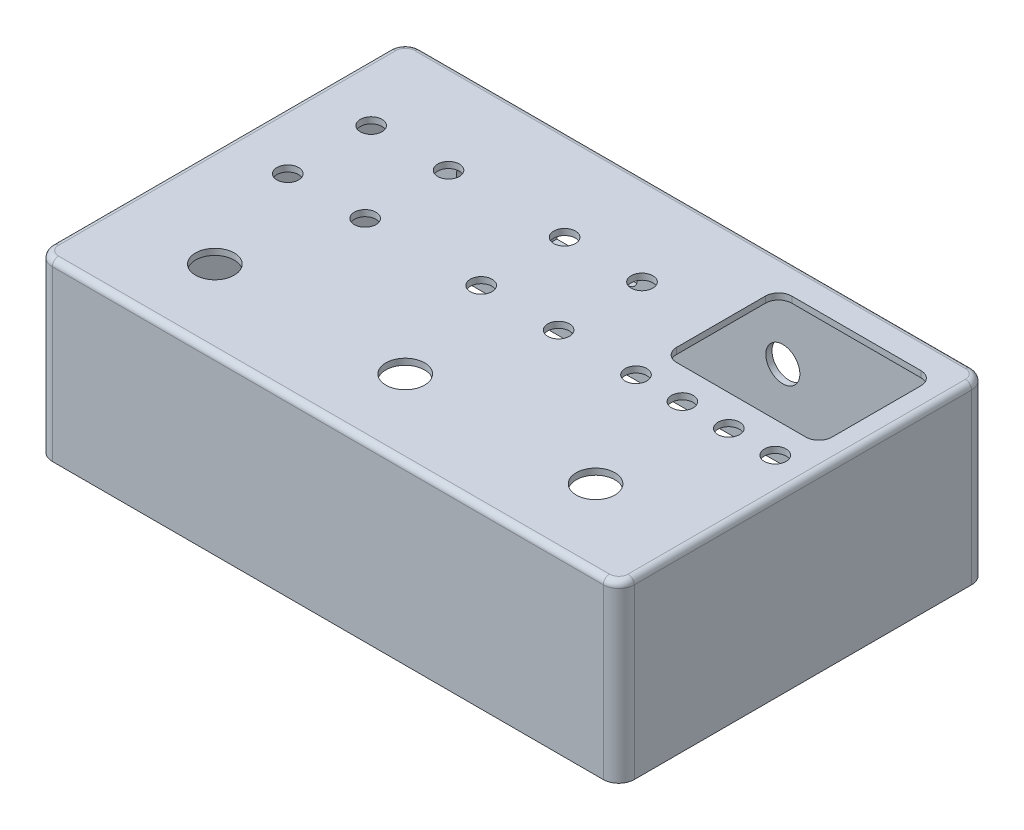
SolidWorks part; units mm, degrees
ref_plane "前视基准面" through (0, 0, 0) normal (0, 0, 1) x (1, 0, 0)
ref_plane "上视基准面" through (0, 0, 0) normal (0, 1, 0) x (1, 0, 0)
ref_plane "右视基准面" through (0, 0, 0) normal (1, 0, 0) x (0, 0, -1)
sketch "草图1" plane through (0, 0, 0) normal (0, 1, 0) x (1, 0, 0)
  line L0 (-67.19, 26.9473) -> (101.81, 26.9473) construction
  line L1 (-86.19, 56.9473) -> (101.81, 56.9473)
  line L2 (-86.19, 56.9473) -> (-86.19, -62.0527)
  line L3 (-86.19, -62.0527) -> (101.81, -62.0527)
  line L4 (101.81, 56.9473) -> (101.81, -62.0527)
  line L5 (-86.19, 26.9473) -> (-67.19, 26.9473) construction
  line L6 (-86.19, 0) -> (101.81, 0) construction
  line L7 (-86.19, -37.0527) -> (101.81, -37.0527) construction
  line L9 (48.445, 46.9473) -> (90.175, 46.9473)
  line L10 (44.445, 42.9473) -> (44.445, 14.2473)
  line L11 (48.445, 10.2473) -> (90.175, 10.2473)
  line L12 (94.175, 42.9473) -> (94.175, 14.2473)
  circle A0 centre (-67.19, 26.9473) radius 3.5
  circle A1 centre (-42.19, 26.9473) radius 3.5
  circle A2 centre (-67.19, 0) radius 3.5
  circle A3 centre (-42.19, 0) radius 3.5
  circle A4 centre (-4.69, 26.9473) radius 3.5
  circle A5 centre (20.31, 26.9473) radius 3.5
  circle A6 centre (-4.69, 0) radius 3.5
  circle A7 centre (20.31, 0) radius 3.5
  circle A8 centre (45.31, 0) radius 3.5
  circle A9 centre (60.31, 0) radius 3.5
  circle A10 centre (75.31, 0) radius 3.5
  circle A11 centre (90.31, 0) radius 3.5
  circle A12 centre (-53.69, -37.0527) radius 6.25
  circle A13 centre (7.81, -37.0527) radius 6.25
  circle A14 centre (69.31, -37.0527) radius 6.25
  arc A15 (90.175, 46.9473) -> (94.175, 42.9473) centre (90.175, 42.9473) cw
  arc A16 (48.445, 46.9473) -> (44.445, 42.9473) centre (48.445, 42.9473) ccw
  arc A17 (90.175, 10.2473) -> (94.175, 14.2473) centre (90.175, 14.2473) ccw
  arc A18 (44.445, 14.2473) -> (48.445, 10.2473) centre (48.445, 14.2473) ccw
  point P43 (69.31, 46.9473)
  point P44 (43.191, 0)
  point P49 (94.175, 46.9473)
  point P52 (44.445, 46.9473)
  point P55 (94.175, 10.2473)
  dimension "D3" = 30
  dimension "D12" = 7
  dimension "D16" = 12.5
  dimension "D19" = 49.73
  dimension "D23" = 4
  dimension "D1" = 188
  dimension "D2" = 119
  dimension "D4" = 19
  dimension "D5" = 25
  dimension "D6" = 25
  dimension "D7" = 37.5
  dimension "D8" = 25
  dimension "D9" = 15
  dimension "D10" = 15
  dimension "D11" = 15
  dimension "D13" = 32.5
  dimension "D14" = 61.5
  dimension "D15" = 61.5
  dimension "D18" = 19
  dimension "D20" = 36.7
  dimension "D21" = 10
  dimension "D22" = 25
extrude "凸台-拉伸1" add sketch "草图1" along normal blind 56.5
sketch "草图3" plane through (0, 0, 0) normal (0, -1, 0) x (1, 0, 0)
  line L1 (98.81, -53.9473) -> (-83.19, -53.9473)
  line L2 (98.81, -53.9473) -> (98.81, 59.0527)
  line L3 (98.81, 59.0527) -> (-83.19, 59.0527)
  line L4 (-86.19, 62.0527) -> (-86.19, -56.9473)
  line L5 (-86.19, -56.9473) -> (101.81, -56.9473)
  line L6 (101.81, -56.9473) -> (101.81, 62.0527)
  line L7 (101.81, 62.0527) -> (-86.19, 62.0527)
  line L8 (-86.19, 62.0527) -> (-86.19, -56.9473)
  line L9 (-86.19, -56.9473) -> (101.81, -56.9473)
  line L10 (101.81, -56.9473) -> (101.81, 62.0527)
  line L11 (101.81, 62.0527) -> (-86.19, 62.0527)
  line L12 (-83.19, -53.9473) -> (-83.19, 59.0527)
  circle M9 centre (69.31, 37.0527) radius 6.25
  circle M10 centre (7.81, 37.0527) radius 6.25
  circle M11 centre (-53.69, 37.0527) radius 6.25
  circle M12 centre (90.31, 0) radius 3.5
  circle M13 centre (75.31, 0) radius 3.5
  circle M14 centre (60.31, 0) radius 3.5
  circle M15 centre (45.31, 0) radius 3.5
  circle M16 centre (20.31, 0) radius 3.5
  circle M17 centre (-4.69, 0) radius 3.5
  circle M18 centre (20.31, -26.9473) radius 3.5
  circle M19 centre (-4.69, -26.9473) radius 3.5
  circle M20 centre (-42.19, 0) radius 3.5
  circle M21 centre (-67.19, 0) radius 3.5
  circle M22 centre (-42.19, -26.9473) radius 3.5
  circle M23 centre (-67.19, -26.9473) radius 3.5
  arc M28 (94.175, -42.9473) -> (90.175, -46.9473) centre (90.175, -42.9473) cw
  line M29 (90.175, -46.9473) -> (48.445, -46.9473)
  arc M30 (48.445, -46.9473) -> (44.445, -42.9473) centre (48.445, -42.9473) cw
  line M31 (44.445, -42.9473) -> (44.445, -14.2473)
  arc M32 (44.445, -14.2473) -> (48.445, -10.2473) centre (48.445, -14.2473) cw
  line M33 (48.445, -10.2473) -> (90.175, -10.2473)
  arc M34 (90.175, -10.2473) -> (94.175, -14.2473) centre (90.175, -14.2473) cw
  line M35 (94.175, -14.2473) -> (94.175, -42.9473)
  dimension "D2" = 3
  dimension "D3" = 3
  dimension "D4" = 3
  dimension "D5" = 3
  dimension "D1" = 0
extrude "切除-拉伸2" cut sketch "草图3" against normal offset from surface (53.5 mm away) 3 contours L12 L1 L2 L3 M10 M12 M14 M16 M18 M20 M22 M35 M28 M29 M30 M31 M32 M33 M34 M23 M21 M19 M17 M15 M13 M11 M9 region at (1.6167, 0, 5.2891) up to face at (7.81, 56.5, 43.3027)
sketch "草图4" plane through (0, 56.5, 0) normal (0, 1, 0) x (1, 0, 0)
  line L0 (90.175, 46.9473) -> (48.445, 46.9473)
  line L1 (90.175, 46.9473) -> (48.445, 46.9473)
  line L2 (44.445, 42.9473) -> (44.445, 14.2473)
  line L3 (44.445, 42.9473) -> (44.445, 14.2473)
  line L4 (94.175, 14.2473) -> (94.175, 42.9473)
  line L5 (94.175, 14.2473) -> (94.175, 42.9473)
  line L6 (48.445, 10.2473) -> (90.175, 10.2473)
  line L7 (48.445, 10.2473) -> (90.175, 10.2473)
  arc A0 (48.445, 46.9473) -> (44.445, 42.9473) centre (48.445, 42.9473) ccw
  arc A1 (48.445, 46.9473) -> (44.445, 42.9473) centre (48.445, 42.9473) ccw
  arc A2 (44.445, 14.2473) -> (48.445, 10.2473) centre (48.445, 14.2473) ccw
  arc A3 (44.445, 14.2473) -> (48.445, 10.2473) centre (48.445, 14.2473) ccw
  arc A4 (94.175, 42.9473) -> (90.175, 46.9473) centre (90.175, 42.9473) ccw
  arc A5 (94.175, 42.9473) -> (90.175, 46.9473) centre (90.175, 42.9473) ccw
  arc A6 (90.175, 10.2473) -> (94.175, 14.2473) centre (90.175, 14.2473) ccw
  arc A7 (90.175, 10.2473) -> (94.175, 14.2473) centre (90.175, 14.2473) ccw
extrude "切除-拉伸-薄壁1" cut sketch "草图4" against normal blind 3 thin thin type one direction wall 0.25
fillet "圆角1" radius 5 8 edges at (-86.19, 28.25, -56.9473) (-86.19, 28.25, 62.0527) (-83.19, 26.75, 59.0527) (98.81, 26.75, -53.9473) (101.81, 28.25, -56.9473) (101.81, 28.25, 62.0527) (98.81, 26.75, 59.0527) (-83.19, 26.75, -53.9473)
sketch "草图5" plane through (0, 53.5, 0) normal (0, -1, 0) x (1, 0, 0)
  line L0 (93.81, 59.0527) -> (-78.19, 59.0527) construction
  line L1 (-80.69, -51.4473) -> (96.31, -51.4473)
  line L2 (-80.69, -51.4473) -> (-80.69, 56.5527)
  line L3 (-80.69, 56.5527) -> (96.31, 56.5527)
  line L4 (96.31, -51.4473) -> (96.31, 56.5527)
  line L5 (-83.19, -48.9473) -> (-83.19, 54.0527) construction
  line L6 (98.81, -48.9473) -> (98.81, 54.0527) construction
  line L7 (93.81, -53.9473) -> (-78.19, -53.9473) construction
  line L8 (96.31, -47.9473) -> (92.5653, -47.9473) construction
  circle A0 centre (-80.69, -51.4473) radius 3.5
  circle A1 centre (-80.69, 56.5527) radius 3.5
  circle A2 centre (96.31, 56.5527) radius 3.5
  circle A3 centre (96.31, -51.4473) radius 3.5
  arc M34 (-78.19, 59.0527) -> (-83.19, 54.0527) centre (-78.19, 54.0527) ccw
  arc M36 (-83.19, -48.9473) -> (-78.19, -53.9473) centre (-78.19, -48.9473) ccw
  arc M38 (93.81, -53.9473) -> (98.81, -48.9473) centre (93.81, -48.9473) ccw
  arc M40 (98.81, 54.0527) -> (93.81, 59.0527) centre (93.81, 54.0527) ccw
  dimension "D1" = 2.5
  dimension "D5" = 7
  dimension "D2" = 2.5
  dimension "D3" = 2.5
  dimension "D4" = 2.5
extrude "凸台-拉伸2" add sketch "草图5" along normal up to surface (53.5 mm away) contours L3 A1 L2 M34 | L2 A1 L3 | A0 L1 L2 M36 | L1 A0 L2 | L3 A2 L4 | L4 A2 L3 M40 | L4 A3 L1 | A3 L4 L1 M38 region at (-79.2045, 53.5, -49.9618) region at (-78.94, 53.5, -51.5321) region at (94.8246, 53.5, -49.9618) region at (94.56, 53.5, -51.5321) region at (-82.0128, 53.5, 53.4042) region at (-79.2045, 53.5, 55.0673) region at (94.8246, 53.5, 55.0673) region at (96.3949, 53.5, 54.8027) up to face at (7.81, 0, 2.5527)
sketch "草图6" plane through (0, 0, 0) normal (0, -1, 0) x (1, 0, 0)
  circle A0 centre (96.31, -51.4473) radius 2.25
  circle A1 centre (96.31, 56.5527) radius 2.25
  circle A2 centre (-80.69, 56.5527) radius 2.25
  circle A3 centre (-80.69, -51.4473) radius 2.25
  dimension "D1" = 4.5
extrude "切除-拉伸3" cut sketch "草图6" against normal blind 20
fillet "圆角2" radius 2 8 edges at (-84.7255, 56.5, 60.5882) (-84.7255, 56.5, -55.4828) (100.3456, 56.5, -55.4828) (100.3456, 56.5, 60.5882) (101.81, 56.5, 2.5527) (7.81, 56.5, -56.9473) (-86.19, 56.5, 2.5527) (7.81, 56.5, 62.0527)
sketch "草图7" plane through (0, 0, -56.9473) normal (0, 0, -1) x (-1, 0, 0)
  line L0 (-96.81, 28.25) -> (81.19, 28.25) construction
  line L3 (-96.81, 54.5) -> (-96.81, 0) construction
  line L4 (81.19, 0) -> (81.19, 54.5) construction
  line L5 (-96.81, 56.5) -> (81.19, 56.5) construction
  line L8 (27.19, 31.75) -> (37.19, 31.75)
  line L9 (27.19, 31.75) -> (27.19, 24.75)
  line L10 (27.19, 24.75) -> (37.19, 24.75)
  line L11 (37.19, 31.75) -> (37.19, 24.75)
  line L12 (23.69, 30) -> (40.69, 30)
  line L13 (23.69, 30) -> (23.69, 26.5)
  line L14 (23.69, 26.5) -> (40.69, 26.5)
  line L15 (40.69, 30) -> (40.69, 26.5)
  circle A0 centre (-7.81, 28.25) radius 5.5
  circle A1 centre (62.19, 28.25) radius 5.5
  circle A3 centre (23.69, 28.25) radius 1.75
  circle A4 centre (40.69, 28.25) radius 1.75
  circle A5 centre (-37.81, 28.25) radius 5.5
  circle A6 centre (-77.81, 28.25) radius 5.5
  circle A7 centre (12.19, 28.25) radius 3
  point P14 (27.19, 28.25)
  point P21 (32.19, 31.75)
  point P22 (-7.81, 28.25)
  point P29 (32.19, 30)
  dimension "D2" = 30
  dimension "D5" = 11
  dimension "D6" = 11
  dimension "D7" = 3.5
  dimension "D3" = 3.5
  dimension "D11" = 11
  dimension "D14" = 6
  dimension "D1" = 28.25
  dimension "D4" = 17
  dimension "D8" = 3.5
  dimension "D9" = 7
  dimension "D10" = 40
  dimension "D12" = 30
  dimension "D13" = 40
  dimension "D15" = 20
  dimension "D16" = 10
extrude "切除-拉伸4" cut sketch "草图7" against normal blind 20 contours A1 L0 | A6 L0 | L0 A6 | A5 L0 | L0 A5 | A7 L0 | L8 L11 L10 L9 | A3 | A4 | A7 | A1 region at (77.81, 30.5843, -56.9473) region at (-62.19, 30.5843, -56.9473) region at (-12.19, 29.5232, -56.9473) region at (37.81, 30.5843, -56.9473) region at (37.81, 25.9157, -56.9473) region at (77.81, 25.9157, -56.9473)
sketch "草图8" plane through (-86.19, 0, 0) normal (-1, 0, 0) x (0, 0, 1)
  line L0 (-56.9473, 0) -> (-56.9473, 54.5) construction
  line L1 (-51.9473, 56.5) -> (57.0527, 56.5) construction
  circle A0 centre (-31.9473, 37.75) radius 5
  dimension "D1" = 25
  dimension "D3" = 10
  dimension "D2" = 18.75
sketch "草图10" plane through (0, 53.5, 0) normal (0, -1, 0) x (1, 0, 0)
  line L4 (98.81, -48.9473) -> (98.81, 54.0527)
  line L5 (93.81, 59.0527) -> (-78.19, 59.0527)
  line L6 (-83.19, 54.0527) -> (-83.19, -48.9473)
  line L7 (-78.19, -53.9473) -> (93.81, -53.9473)
  line L8 (98.81, -48.9473) -> (98.81, 54.0527)
  line L9 (93.81, 59.0527) -> (-78.19, 59.0527)
  line L10 (-83.19, 54.0527) -> (-83.19, -48.9473)
  line L11 (-78.19, -53.9473) -> (93.81, -53.9473)
  arc A12 (98.8098, -48.9975) -> (93.8603, -53.947) centre (96.31, -51.4473) ccw
  arc A13 (98.8098, -48.9975) -> (98.81, -48.9473) centre (93.81, -48.9473) ccw
  arc A14 (98.81, 54.0527) -> (98.8098, 54.103) centre (93.81, 54.0527) ccw
  arc A15 (93.8603, 59.0525) -> (98.8098, 54.103) centre (96.31, 56.5527) ccw
  arc A16 (93.8603, 59.0525) -> (93.81, 59.0527) centre (93.81, 54.0527) ccw
  arc A17 (-78.19, 59.0527) -> (-78.2402, 59.0525) centre (-78.19, 54.0527) ccw
  arc A18 (-83.1897, 54.103) -> (-78.2402, 59.0525) centre (-80.69, 56.5527) ccw
  arc A19 (-83.1897, 54.103) -> (-83.19, 54.0527) centre (-78.19, 54.0527) ccw
  arc A20 (-83.19, -48.9473) -> (-83.1897, -48.9975) centre (-78.19, -48.9473) ccw
  arc A21 (-78.2402, -53.947) -> (-83.1897, -48.9975) centre (-80.69, -51.4473) ccw
  arc A22 (-78.2402, -53.947) -> (-78.19, -53.9473) centre (-78.19, -48.9473) ccw
  arc A23 (93.81, -53.9473) -> (93.8603, -53.947) centre (93.81, -48.9473) ccw
  arc A24 (98.8098, -48.9975) -> (93.8603, -53.947) centre (96.31, -51.4473) ccw
  arc A25 (98.8098, -48.9975) -> (98.81, -48.9473) centre (93.81, -48.9473) ccw
  arc A26 (98.81, 54.0527) -> (98.8098, 54.103) centre (93.81, 54.0527) ccw
  arc A27 (93.8603, 59.0525) -> (98.8098, 54.103) centre (96.31, 56.5527) ccw
  arc A28 (93.8603, 59.0525) -> (93.81, 59.0527) centre (93.81, 54.0527) ccw
  arc A29 (-78.19, 59.0527) -> (-78.2402, 59.0525) centre (-78.19, 54.0527) ccw
  arc A30 (-83.1897, 54.103) -> (-78.2402, 59.0525) centre (-80.69, 56.5527) ccw
  arc A31 (-83.1897, 54.103) -> (-83.19, 54.0527) centre (-78.19, 54.0527) ccw
  arc A32 (-83.19, -48.9473) -> (-83.1897, -48.9975) centre (-78.19, -48.9473) ccw
  arc A33 (-78.2402, -53.947) -> (-83.1897, -48.9975) centre (-80.69, -51.4473) ccw
  arc A34 (-78.2402, -53.947) -> (-78.19, -53.9473) centre (-78.19, -48.9473) ccw
  arc A35 (93.81, -53.9473) -> (93.8603, -53.947) centre (93.81, -48.9473) ccw
  dimension "D1" = 0
extrude "切除-拉伸5" cut sketch "草图10" against normal blind 1
sketch "草图11" plane through (0, 0, -53.9473) normal (0, 0, 1) x (1, 0, 0)
  line L4 (-78.19, 0) -> (93.81, 0)
  line L5 (93.81, 0) -> (93.81, 54.5)
  line L6 (93.81, 54.5) -> (-78.19, 54.5)
  line L7 (-78.19, 54.5) -> (-78.19, 0)
  line L8 (-78.19, 0) -> (93.81, 0)
  line L9 (93.81, 0) -> (93.81, 54.5)
  line L10 (93.81, 54.5) -> (-78.19, 54.5)
  line L11 (-78.19, 54.5) -> (-78.19, 0)
  dimension "D1" = 0
extrude "切除-拉伸6" cut sketch "草图11" against normal blind 1 contours L8 L9 L10 L11
sketch "草图9" plane through (0, 0, 0) normal (0, -1, 0) x (1, 0, 0)
  line L0 (-83.19, -48.9473) -> (-83.19, 54.0527) construction
  line L1 (93.81, 59.0527) -> (-78.19, 59.0527) construction
  line L2 (93.81, -53.9473) -> (-78.19, -53.9473) construction
  line L3 (98.81, -48.9473) -> (98.81, 54.0527) construction
  line L4 (-86.19, 57.0527) -> (-86.19, -51.9473)
  line L5 (-81.19, -56.9473) -> (96.81, -56.9473)
  line L6 (101.81, -51.9473) -> (101.81, 57.0527)
  line L7 (96.81, 62.0527) -> (-81.19, 62.0527)
  line L8 (-86.19, 57.0527) -> (-86.19, -51.9473)
  line L9 (-81.19, -56.9473) -> (96.81, -56.9473)
  line L10 (101.81, -51.9473) -> (101.81, 57.0527)
  line L11 (96.81, 62.0527) -> (-81.19, 62.0527)
  line L12 (-83.19, -48.9473) -> (-83.19, 54.0527)
  line L13 (93.81, 59.0527) -> (-78.19, 59.0527)
  line L14 (93.81, -53.9473) -> (-78.19, -53.9473)
  line L15 (98.81, -48.9473) -> (98.81, 54.0527)
  arc A0 (-78.2402, -53.947) -> (-83.1897, -48.9975) centre (-80.69, -51.4473) ccw construction
  arc A1 (-83.1897, 54.103) -> (-78.2402, 59.0525) centre (-80.69, 56.5527) ccw construction
  arc A2 (93.8603, 59.0525) -> (98.8098, 54.103) centre (96.31, 56.5527) ccw construction
  arc A3 (98.8098, -48.9975) -> (93.8603, -53.947) centre (96.31, -51.4473) ccw construction
  arc A12 (-78.2402, -53.947) -> (-83.1897, -48.9975) centre (-80.69, -51.4473) ccw
  arc A13 (-83.1897, 54.103) -> (-78.2402, 59.0525) centre (-80.69, 56.5527) ccw
  arc A14 (93.8603, 59.0525) -> (98.8098, 54.103) centre (96.31, 56.5527) ccw
  arc A15 (98.8098, -48.9975) -> (93.8603, -53.947) centre (96.31, -51.4473) ccw
  arc A16 (93.8603, 59.0525) -> (93.81, 59.0527) centre (93.81, 54.0527) ccw construction
  arc A17 (93.8603, 59.0525) -> (93.81, 59.0527) centre (93.81, 54.0527) ccw
  arc A18 (98.81, 54.0527) -> (98.8098, 54.103) centre (93.81, 54.0527) ccw construction
  arc A19 (98.81, 54.0527) -> (98.8098, 54.103) centre (93.81, 54.0527) ccw
  arc A20 (98.8098, -48.9975) -> (98.81, -48.9473) centre (93.81, -48.9473) ccw construction
  arc A21 (98.8098, -48.9975) -> (98.81, -48.9473) centre (93.81, -48.9473) ccw
  arc A22 (93.81, -53.9473) -> (93.8603, -53.947) centre (93.81, -48.9473) ccw construction
  arc A23 (93.81, -53.9473) -> (93.8603, -53.947) centre (93.81, -48.9473) ccw
  arc A24 (-83.19, -48.9473) -> (-83.1897, -48.9975) centre (-78.19, -48.9473) ccw construction
  arc A25 (-83.19, -48.9473) -> (-83.1897, -48.9975) centre (-78.19, -48.9473) ccw
  arc A26 (-78.2402, -53.947) -> (-78.19, -53.9473) centre (-78.19, -48.9473) ccw construction
  arc A27 (-78.2402, -53.947) -> (-78.19, -53.9473) centre (-78.19, -48.9473) ccw
  arc A28 (-83.1897, 54.103) -> (-83.19, 54.0527) centre (-78.19, 54.0527) ccw construction
  arc A29 (-83.1897, 54.103) -> (-83.19, 54.0527) centre (-78.19, 54.0527) ccw
  arc A30 (-78.19, 59.0527) -> (-78.2402, 59.0525) centre (-78.19, 54.0527) ccw construction
  arc A31 (-78.19, 59.0527) -> (-78.2402, 59.0525) centre (-78.19, 54.0527) ccw
  arc A32 (-86.19, -51.9473) -> (-81.19, -56.9473) centre (-81.19, -51.9473) ccw
  arc A33 (-86.19, -51.9473) -> (-81.19, -56.9473) centre (-81.19, -51.9473) ccw
  arc A34 (96.81, -56.9473) -> (101.81, -51.9473) centre (96.81, -51.9473) ccw
  arc A35 (96.81, -56.9473) -> (101.81, -51.9473) centre (96.81, -51.9473) ccw
  arc A36 (101.81, 57.0527) -> (96.81, 62.0527) centre (96.81, 57.0527) ccw
  arc A37 (101.81, 57.0527) -> (96.81, 62.0527) centre (96.81, 57.0527) ccw
  arc A38 (-81.19, 62.0527) -> (-86.19, 57.0527) centre (-81.19, 57.0527) ccw
  arc A39 (-81.19, 62.0527) -> (-86.19, 57.0527) centre (-81.19, 57.0527) ccw
  dimension "D1" = 0
